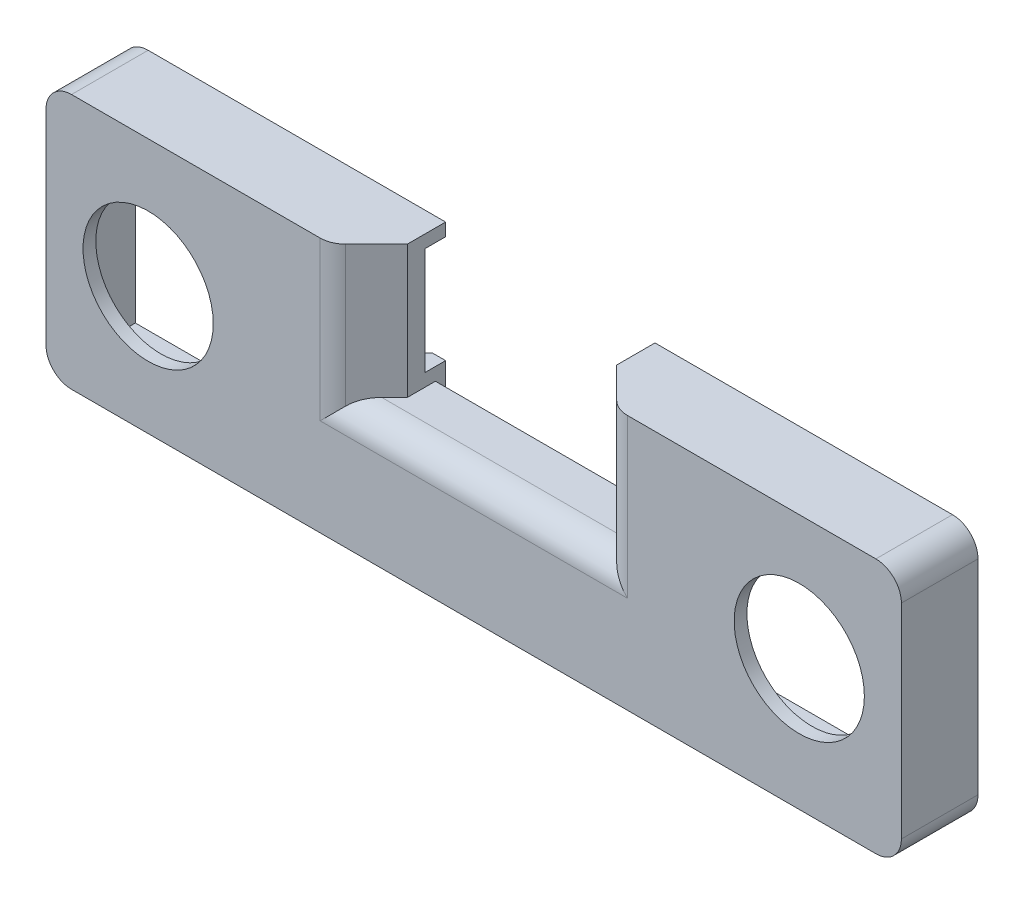
SolidWorks part; units mm, degrees
ref_plane "Front Plane" through (0, 0, 0) normal (0, 0, 1) x (1, 0, 0)
ref_plane "Top Plane" through (0, 0, 0) normal (0, 1, 0) x (1, 0, 0)
ref_plane "Right Plane" through (0, 0, 0) normal (1, 0, 0) x (0, 0, -1)
sketch "Sketch1" plane through (0, 0, 0) normal (0, 0, 1) x (1, 0, 0)
  line L0 (0, 0) -> (0, 24) construction
  line L1 (-167.5, -50) -> (167.5, -50)
  line L2 (-167.5, -50) -> (-167.5, 50)
  line L3 (-167.5, 50) -> (-41, 50)
  line L4 (167.5, -50) -> (167.5, 50)
  line L5 (-167.5, -50) -> (167.5, 50) construction
  line L6 (-167.5, 50) -> (167.5, -50) construction
  line L7 (41, 50) -> (167.5, 50)
  line L8 (-41, -2) -> (41, -2)
  line L9 (-41, -2) -> (-41, 50)
  line L11 (41, -2) -> (41, 50)
  line L12 (-41, -2) -> (41, 50) construction
  line L13 (-41, 50) -> (41, -2) construction
  line L14 (0, 0) -> (-167.5, 0) construction
  line L15 (0, 0) -> (167.5, 1.5601) construction
  circle A0 centre (-127.5, 0) radius 25.5
  circle A1 centre (127.5, 1.1875) radius 25.5
  point P0 (0, 0)
  point P8 (0, 24)
  dimension "D5" = 40
  dimension "D6" = 40
  dimension "D1" = 335
  dimension "D2" = 100
  dimension "D3" = 82
  dimension "D4" = 52
extrude "Boss-Extrude1" add sketch "Sketch1" against normal blind 5
sketch "Sketch2" plane through (0, 0, -5) normal (0, 0, -1) x (-1, 0, 0)
  line L0 (167.5, -50) -> (-167.5, -50) construction
  line L1 (-167.5, 50) -> (-162.5, 50)
  line L2 (-167.5, 50) -> (-167.5, -50)
  line L3 (-167.5, -50) -> (-162.5, -50)
  line L4 (-162.5, 45) -> (-162.5, -45)
  line L5 (-41, 50) -> (-41, -2) construction
  line L6 (-162.5, 50) -> (-41, 50)
  line L8 (-162.5, 45) -> (-46, 45)
  line L9 (-41, 50) -> (-41, 45)
  line L11 (167.5, 50) -> (162.5, 50)
  line L12 (167.5, 50) -> (167.5, -50)
  line L13 (167.5, -50) -> (162.5, -50)
  line L14 (162.5, 45) -> (162.5, -45)
  line L15 (41, 50) -> (162.5, 50)
  line L16 (41, 50) -> (41, 45)
  line L17 (46, 45) -> (162.5, 45)
  line L19 (-162.5, -50) -> (162.5, -50)
  line L21 (-162.5, -45) -> (162.5, -45)
  line L23 (-41, -2) -> (41, -2)
  line L25 (-41, -7) -> (41, -7)
  line L27 (-41, -7) -> (-46, -7)
  line L28 (-41, -2) -> (-41, 45)
  line L30 (-46, -7) -> (-46, 45)
  line L31 (41, -7) -> (46, -7)
  line L32 (41, -2) -> (41, 45)
  line L34 (46, -7) -> (46, 45)
  dimension "D1" = 5
  dimension "D2" = 5
  dimension "D3" = 5
  dimension "D4" = 5
  dimension "D5" = 5
  dimension "D6" = 5
  dimension "D7" = 5
  dimension "D8" = 5
extrude "Boss-Extrude2" add sketch "Sketch2" along normal blind 25
fillet "Fillet1" radius 10 4 edges at (-167.5, 50, -15) (-167.5, -50, -15) (167.5, -50, -15) (167.5, 50, -15)
chamfer "Chamfer3" distance 25 angle 45 2 edges at (-46, 19, -5) (46, 19, -5)
chamfer "Chamfer4" distance 15 angle 45 2 edges at (41, 24, 0) (-41, 24, 0)
sketch "Sketch3" plane through (-41, 0, 0) normal (1, 0, 0) x (0, 0, -1)
  line L0 (30, 50) -> (30, -2) construction
  line L1 (30, 45) -> (22, 45)
  line L2 (30, 45) -> (30, 3)
  line L3 (30, 3) -> (22, 3)
  line L4 (22, 45) -> (22, 3)
  line L5 (30, 50) -> (15, 50) construction
  line L6 (30, -2) -> (15, -2) construction
  dimension "D1" = 5
  dimension "D2" = 5
  dimension "D3" = 8
extrude "Cut-Extrude1" cut sketch "Sketch3" against normal blind 25
sketch "Sketch4" plane through (41, 0, 0) normal (-1, 0, 0) x (0, 0, 1)
  line L0 (-30, -2) -> (-30, 50) construction
  line L1 (-30, 45) -> (-22, 45)
  line L2 (-30, 45) -> (-30, 3)
  line L3 (-30, 3) -> (-22, 3)
  line L4 (-22, 45) -> (-22, 3)
  line L5 (-30, 50) -> (-15, 50) construction
  line L6 (-30, -2) -> (-15, -2) construction
  point P8 (-22.5, 50)
  dimension "D1" = 5
  dimension "D2" = 5
  dimension "D3" = 8
extrude "Cut-Extrude2" cut sketch "Sketch4" against normal blind 25
fillet "Fillet2" radius 10 3 edges at (0, -2, 0) (56, 24, 0) (-56, 24, 0)
sketch "Sketch5" plane through (0, -2, 0) normal (0, 1, 0) x (1, 0, 0)
  line L0 (41, 30) -> (41, 15) construction
  line L1 (-41, 30) -> (41, 30)
  line L2 (-41, 30) -> (-41, 26)
  line L3 (-41, 26) -> (41, 26)
  line L4 (41, 30) -> (41, 26)
  dimension "D1" = 4
extrude "Cut-Extrude3" cut sketch "Sketch5" against normal blind 10
